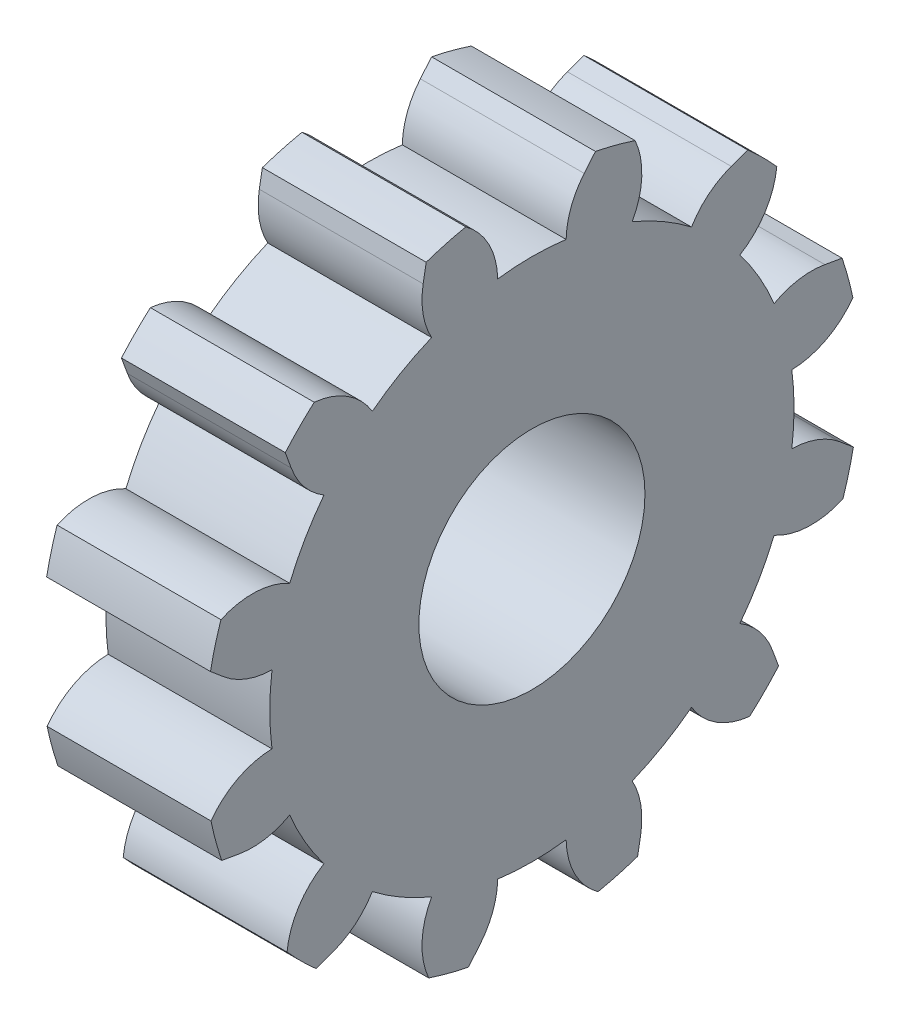
SolidWorks part; units mm, degrees
ref_plane "Front Plane" through (0, 0, 0) normal (0, 0, 1) x (1, 0, 0)
ref_plane "Top Plane" through (0, 0, 0) normal (0, 1, 0) x (1, 0, 0)
ref_plane "Right Plane" through (0, 0, 0) normal (1, 0, 0) x (0, 0, -1)
sketch "Sketch3" plane through (0, 0, 0) normal (1, 0, 0) x (0, 0, -1)
  circle A0 centre (0, 0) radius 10
  circle A1 centre (0, 0) radius 3.45
  circle A2 centre (0, 0) radius 9
  circle A3 centre (0, 0) radius 8
  dimension "D1" = 20
  dimension "D2" = 18
  dimension "D3" = 6.9
  dimension "D4" = 16
extrude "Boss-Extrude1" add sketch "Sketch3" along normal blind 5 contours A1 | A3 A1 | A2 A3 | A0 A2 region at (0, 0, 9.7172) region at (0, 0, 0) region at (0, 0, 8.7454) region at (0, 0, 7.7737)
sketch "Gear_Profile" plane through (0, 0, 0) normal (-1, 0, 0) x (0, 0, 1)
  line L0 (0, 0) -> (0, 13.9827) construction
  line L1 (0, 7.5) -> (-2.6395, 10.6456)
  line L2 (-2.7176, 10.1422) -> (0, 0)
  line L3 (0, 0) -> (2.7176, 10.1422)
  line L4 (-1.0442, 7.9316) -> (0, 0)
  line L5 (1.0442, 7.9316) -> (0, 0)
  arc A0 (-1.0442, 7.9316) -> (1.0442, 7.9316) centre (0, 0) cw
  circle A1 centre (0, 0) radius 8 construction
  arc A2 (-2.7176, 10.1422) -> (2.7176, 10.1422) centre (0, 0) cw
  circle A3 centre (0, 0) radius 10 construction
  arc A4 (-2.7176, 10.1422) -> (-1.0442, 7.9316) centre (-3.4017, 7.8857) cw
  arc A5 (2.7176, 10.1422) -> (1.0442, 7.9316) centre (3.4017, 7.8857) ccw
  point P14 (-1.3705, 11.371)
  circle M7 centre (0, 0) radius 10
  dimension "D1" = 0.5
  dimension "D2" = 7.5
  dimension "D3" = 40
  dimension "D4" = 30
  dimension "D5" = 15
extrude "Cut-Extrude1" cut sketch "Gear_Profile" against normal blind 5 contours A0 L0 L1 M7 | L1 A4 A0 | L0 A0 A5 M7 region at (0, 8.3419, -0.9131) region at (0, 9.0788, 0.7112) region at (0, 9.18, -0.6767)
pattern_circular "CirPattern1" count 12 over 360 about axis through (5, 0, 0) along (-1, 0, 0) of "Cut-Extrude1" reverse direction yes
extrude "Cut-Extrude3" cut sketch "Sketch3<3>" along normal blind 5 contours A1 region at (0, 0, 0)
sketch "Sketch3<3>" plane through (0, 0, 0) normal (1, 0, 0) x (0, 0, -1) same geometry as "Sketch3"
